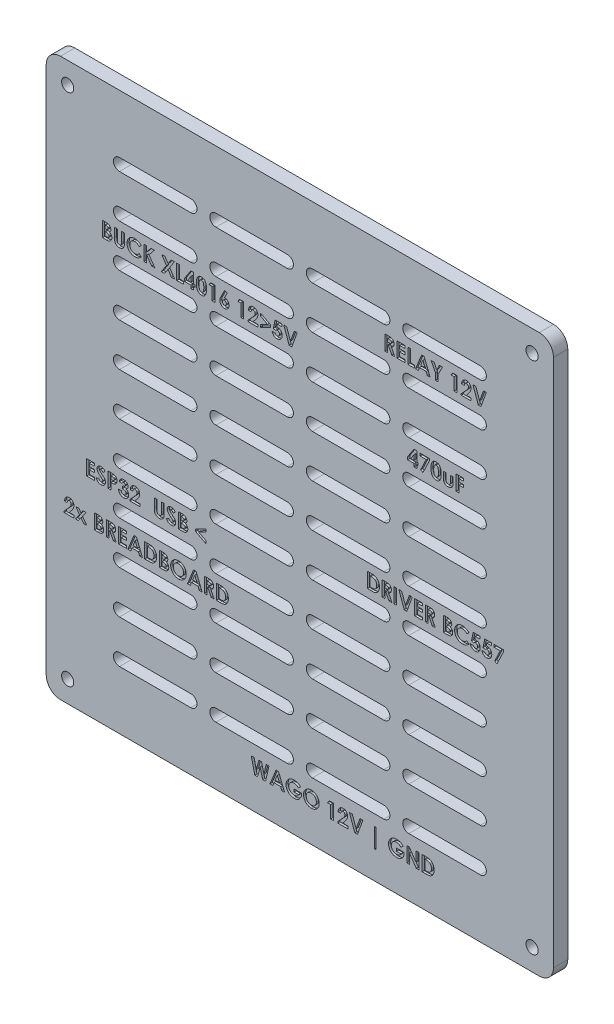
SolidWorks part; units mm, degrees
ref_plane "Front Plane" through (0, 0, 0) normal (0, 0, 1) x (1, 0, 0)
ref_plane "Top Plane" through (0, 0, 0) normal (0, 1, 0) x (1, 0, 0)
ref_plane "Right Plane" through (0, 0, 0) normal (1, 0, 0) x (0, 0, -1)
sketch "Sketch1" plane through (0, 0, 0) normal (0, 0, 1) x (1, 0, 0)
  line L0 (-67, 40) -> (67, 40)
  line L1 (71, 44) -> (71, 192)
  line L2 (67, 196) -> (-67, 196)
  line L3 (-71, 192) -> (-71, 44)
  arc A0 (-71, 44) -> (-67, 40) centre (-67, 44) ccw
  arc A1 (67, 40) -> (71, 44) centre (67, 44) ccw
  arc A2 (71, 192) -> (67, 196) centre (67, 192) ccw
  arc A3 (-67, 196) -> (-71, 192) centre (-67, 192) ccw
extrude "Plate" add sketch "Sketch1" along normal blind 4
sketch "Sketch2" plane through (0, 0, 0) normal (0, 0, 1) x (1, 0, 0)
  line L0 (-50.5, 58) -> (-30.5, 58) construction
  line L1 (-50.5, 59.7) -> (-30.5, 59.7)
  line L2 (-50.5, 56.3) -> (-30.5, 56.3)
  line L3 (-23.5, 58) -> (-3.5, 58) construction
  line L4 (-23.5, 59.7) -> (-3.5, 59.7)
  line L5 (-23.5, 56.3) -> (-3.5, 56.3)
  line L6 (3.5, 58) -> (23.5, 58) construction
  line L7 (3.5, 59.7) -> (23.5, 59.7)
  line L8 (3.5, 56.3) -> (23.5, 56.3)
  line L9 (30.5, 58) -> (50.5, 58) construction
  line L10 (30.5, 59.7) -> (50.5, 59.7)
  line L11 (30.5, 56.3) -> (50.5, 56.3)
  line L12 (-50.5, 70) -> (-30.5, 70) construction
  line L13 (-50.5, 71.7) -> (-30.5, 71.7)
  line L14 (-50.5, 68.3) -> (-30.5, 68.3)
  line L15 (-23.5, 70) -> (-3.5, 70) construction
  line L16 (-23.5, 71.7) -> (-3.5, 71.7)
  line L17 (-23.5, 68.3) -> (-3.5, 68.3)
  line L18 (3.5, 70) -> (23.5, 70) construction
  line L19 (3.5, 71.7) -> (23.5, 71.7)
  line L20 (3.5, 68.3) -> (23.5, 68.3)
  line L21 (30.5, 70) -> (50.5, 70) construction
  line L22 (30.5, 71.7) -> (50.5, 71.7)
  line L23 (30.5, 68.3) -> (50.5, 68.3)
  line L24 (-50.5, 82) -> (-30.5, 82) construction
  line L25 (-50.5, 83.7) -> (-30.5, 83.7)
  line L26 (-50.5, 80.3) -> (-30.5, 80.3)
  line L27 (-23.5, 82) -> (-3.5, 82) construction
  line L28 (-23.5, 83.7) -> (-3.5, 83.7)
  line L29 (-23.5, 80.3) -> (-3.5, 80.3)
  line L30 (3.5, 82) -> (23.5, 82) construction
  line L31 (3.5, 83.7) -> (23.5, 83.7)
  line L32 (3.5, 80.3) -> (23.5, 80.3)
  line L33 (30.5, 82) -> (50.5, 82) construction
  line L34 (30.5, 83.7) -> (50.5, 83.7)
  line L35 (30.5, 80.3) -> (50.5, 80.3)
  line L36 (-50.5, 94) -> (-30.5, 94) construction
  line L37 (-50.5, 95.7) -> (-30.5, 95.7)
  line L38 (-50.5, 92.3) -> (-30.5, 92.3)
  line L39 (-23.5, 94) -> (-3.5, 94) construction
  line L40 (-23.5, 95.7) -> (-3.5, 95.7)
  line L41 (-23.5, 92.3) -> (-3.5, 92.3)
  line L42 (3.5, 94) -> (23.5, 94) construction
  line L43 (3.5, 95.7) -> (23.5, 95.7)
  line L44 (3.5, 92.3) -> (23.5, 92.3)
  line L45 (30.5, 94) -> (50.5, 94) construction
  line L46 (30.5, 95.7) -> (50.5, 95.7)
  line L47 (30.5, 92.3) -> (50.5, 92.3)
  line L48 (-50.5, 106) -> (-30.5, 106) construction
  line L49 (-50.5, 107.7) -> (-30.5, 107.7)
  line L50 (-50.5, 104.3) -> (-30.5, 104.3)
  line L51 (-23.5, 106) -> (-3.5, 106) construction
  line L52 (-23.5, 107.7) -> (-3.5, 107.7)
  line L53 (-23.5, 104.3) -> (-3.5, 104.3)
  line L54 (3.5, 106) -> (23.5, 106) construction
  line L55 (3.5, 107.7) -> (23.5, 107.7)
  line L56 (3.5, 104.3) -> (23.5, 104.3)
  line L57 (30.5, 106) -> (50.5, 106) construction
  line L58 (30.5, 107.7) -> (50.5, 107.7)
  line L59 (30.5, 104.3) -> (50.5, 104.3)
  line L60 (-50.5, 118) -> (-30.5, 118) construction
  line L61 (-50.5, 119.7) -> (-30.5, 119.7)
  line L62 (-50.5, 116.3) -> (-30.5, 116.3)
  line L63 (-23.5, 118) -> (-3.5, 118) construction
  line L64 (-23.5, 119.7) -> (-3.5, 119.7)
  line L65 (-23.5, 116.3) -> (-3.5, 116.3)
  line L66 (3.5, 118) -> (23.5, 118) construction
  line L67 (3.5, 119.7) -> (23.5, 119.7)
  line L68 (3.5, 116.3) -> (23.5, 116.3)
  line L69 (30.5, 118) -> (50.5, 118) construction
  line L70 (30.5, 119.7) -> (50.5, 119.7)
  line L71 (30.5, 116.3) -> (50.5, 116.3)
  line L72 (-50.5, 130) -> (-30.5, 130) construction
  line L73 (-50.5, 131.7) -> (-30.5, 131.7)
  line L74 (-50.5, 128.3) -> (-30.5, 128.3)
  line L75 (-23.5, 130) -> (-3.5, 130) construction
  line L76 (-23.5, 131.7) -> (-3.5, 131.7)
  line L77 (-23.5, 128.3) -> (-3.5, 128.3)
  line L78 (3.5, 130) -> (23.5, 130) construction
  line L79 (3.5, 131.7) -> (23.5, 131.7)
  line L80 (3.5, 128.3) -> (23.5, 128.3)
  line L81 (30.5, 130) -> (50.5, 130) construction
  line L82 (30.5, 131.7) -> (50.5, 131.7)
  line L83 (30.5, 128.3) -> (50.5, 128.3)
  line L84 (-50.5, 142) -> (-30.5, 142) construction
  line L85 (-50.5, 143.7) -> (-30.5, 143.7)
  line L86 (-50.5, 140.3) -> (-30.5, 140.3)
  line L87 (-23.5, 142) -> (-3.5, 142) construction
  line L88 (-23.5, 143.7) -> (-3.5, 143.7)
  line L89 (-23.5, 140.3) -> (-3.5, 140.3)
  line L90 (3.5, 142) -> (23.5, 142) construction
  line L91 (3.5, 143.7) -> (23.5, 143.7)
  line L92 (3.5, 140.3) -> (23.5, 140.3)
  line L93 (30.5, 142) -> (50.5, 142) construction
  line L94 (30.5, 143.7) -> (50.5, 143.7)
  line L95 (30.5, 140.3) -> (50.5, 140.3)
  line L96 (-50.5, 154) -> (-30.5, 154) construction
  line L97 (-50.5, 155.7) -> (-30.5, 155.7)
  line L98 (-50.5, 152.3) -> (-30.5, 152.3)
  line L99 (-23.5, 154) -> (-3.5, 154) construction
  line L100 (-23.5, 155.7) -> (-3.5, 155.7)
  line L101 (-23.5, 152.3) -> (-3.5, 152.3)
  line L102 (3.5, 154) -> (23.5, 154) construction
  line L103 (3.5, 155.7) -> (23.5, 155.7)
  line L104 (3.5, 152.3) -> (23.5, 152.3)
  line L105 (30.5, 154) -> (50.5, 154) construction
  line L106 (30.5, 155.7) -> (50.5, 155.7)
  line L107 (30.5, 152.3) -> (50.5, 152.3)
  line L108 (-50.5, 166) -> (-30.5, 166) construction
  line L109 (-50.5, 167.7) -> (-30.5, 167.7)
  line L110 (-50.5, 164.3) -> (-30.5, 164.3)
  line L111 (-23.5, 166) -> (-3.5, 166) construction
  line L112 (-23.5, 167.7) -> (-3.5, 167.7)
  line L113 (-23.5, 164.3) -> (-3.5, 164.3)
  line L114 (3.5, 166) -> (23.5, 166) construction
  line L115 (3.5, 167.7) -> (23.5, 167.7)
  line L116 (3.5, 164.3) -> (23.5, 164.3)
  line L117 (30.5, 166) -> (50.5, 166) construction
  line L118 (30.5, 167.7) -> (50.5, 167.7)
  line L119 (30.5, 164.3) -> (50.5, 164.3)
  line L120 (-50.5, 178) -> (-30.5, 178) construction
  line L121 (-50.5, 179.7) -> (-30.5, 179.7)
  line L122 (-50.5, 176.3) -> (-30.5, 176.3)
  line L123 (-23.5, 178) -> (-3.5, 178) construction
  line L124 (-23.5, 179.7) -> (-3.5, 179.7)
  line L125 (-23.5, 176.3) -> (-3.5, 176.3)
  line L126 (3.5, 178) -> (23.5, 178) construction
  line L127 (3.5, 179.7) -> (23.5, 179.7)
  line L128 (3.5, 176.3) -> (23.5, 176.3)
  line L129 (30.5, 178) -> (50.5, 178) construction
  line L130 (30.5, 179.7) -> (50.5, 179.7)
  line L131 (30.5, 176.3) -> (50.5, 176.3)
  circle A0 centre (-65, 46) radius 1.7
  circle A1 centre (65, 46) radius 1.7
  circle A2 centre (-65, 190) radius 1.7
  circle A3 centre (65, 190) radius 1.7
  arc A4 (-50.5, 59.7) -> (-50.5, 56.3) centre (-50.5, 58) ccw
  arc A5 (-30.5, 56.3) -> (-30.5, 59.7) centre (-30.5, 58) ccw
  arc A6 (-23.5, 59.7) -> (-23.5, 56.3) centre (-23.5, 58) ccw
  arc A7 (-3.5, 56.3) -> (-3.5, 59.7) centre (-3.5, 58) ccw
  arc A8 (3.5, 59.7) -> (3.5, 56.3) centre (3.5, 58) ccw
  arc A9 (23.5, 56.3) -> (23.5, 59.7) centre (23.5, 58) ccw
  arc A10 (30.5, 59.7) -> (30.5, 56.3) centre (30.5, 58) ccw
  arc A11 (50.5, 56.3) -> (50.5, 59.7) centre (50.5, 58) ccw
  arc A12 (-50.5, 71.7) -> (-50.5, 68.3) centre (-50.5, 70) ccw
  arc A13 (-30.5, 68.3) -> (-30.5, 71.7) centre (-30.5, 70) ccw
  arc A14 (-23.5, 71.7) -> (-23.5, 68.3) centre (-23.5, 70) ccw
  arc A15 (-3.5, 68.3) -> (-3.5, 71.7) centre (-3.5, 70) ccw
  arc A16 (3.5, 71.7) -> (3.5, 68.3) centre (3.5, 70) ccw
  arc A17 (23.5, 68.3) -> (23.5, 71.7) centre (23.5, 70) ccw
  arc A18 (30.5, 71.7) -> (30.5, 68.3) centre (30.5, 70) ccw
  arc A19 (50.5, 68.3) -> (50.5, 71.7) centre (50.5, 70) ccw
  arc A20 (-50.5, 83.7) -> (-50.5, 80.3) centre (-50.5, 82) ccw
  arc A21 (-30.5, 80.3) -> (-30.5, 83.7) centre (-30.5, 82) ccw
  arc A22 (-23.5, 83.7) -> (-23.5, 80.3) centre (-23.5, 82) ccw
  arc A23 (-3.5, 80.3) -> (-3.5, 83.7) centre (-3.5, 82) ccw
  arc A24 (3.5, 83.7) -> (3.5, 80.3) centre (3.5, 82) ccw
  arc A25 (23.5, 80.3) -> (23.5, 83.7) centre (23.5, 82) ccw
  arc A26 (30.5, 83.7) -> (30.5, 80.3) centre (30.5, 82) ccw
  arc A27 (50.5, 80.3) -> (50.5, 83.7) centre (50.5, 82) ccw
  arc A28 (-50.5, 95.7) -> (-50.5, 92.3) centre (-50.5, 94) ccw
  arc A29 (-30.5, 92.3) -> (-30.5, 95.7) centre (-30.5, 94) ccw
  arc A30 (-23.5, 95.7) -> (-23.5, 92.3) centre (-23.5, 94) ccw
  arc A31 (-3.5, 92.3) -> (-3.5, 95.7) centre (-3.5, 94) ccw
  arc A32 (3.5, 95.7) -> (3.5, 92.3) centre (3.5, 94) ccw
  arc A33 (23.5, 92.3) -> (23.5, 95.7) centre (23.5, 94) ccw
  arc A34 (30.5, 95.7) -> (30.5, 92.3) centre (30.5, 94) ccw
  arc A35 (50.5, 92.3) -> (50.5, 95.7) centre (50.5, 94) ccw
  arc A36 (-50.5, 107.7) -> (-50.5, 104.3) centre (-50.5, 106) ccw
  arc A37 (-30.5, 104.3) -> (-30.5, 107.7) centre (-30.5, 106) ccw
  arc A38 (-23.5, 107.7) -> (-23.5, 104.3) centre (-23.5, 106) ccw
  arc A39 (-3.5, 104.3) -> (-3.5, 107.7) centre (-3.5, 106) ccw
  arc A40 (3.5, 107.7) -> (3.5, 104.3) centre (3.5, 106) ccw
  arc A41 (23.5, 104.3) -> (23.5, 107.7) centre (23.5, 106) ccw
  arc A42 (30.5, 107.7) -> (30.5, 104.3) centre (30.5, 106) ccw
  arc A43 (50.5, 104.3) -> (50.5, 107.7) centre (50.5, 106) ccw
  arc A44 (-50.5, 119.7) -> (-50.5, 116.3) centre (-50.5, 118) ccw
  arc A45 (-30.5, 116.3) -> (-30.5, 119.7) centre (-30.5, 118) ccw
  arc A46 (-23.5, 119.7) -> (-23.5, 116.3) centre (-23.5, 118) ccw
  arc A47 (-3.5, 116.3) -> (-3.5, 119.7) centre (-3.5, 118) ccw
  arc A48 (3.5, 119.7) -> (3.5, 116.3) centre (3.5, 118) ccw
  arc A49 (23.5, 116.3) -> (23.5, 119.7) centre (23.5, 118) ccw
  arc A50 (30.5, 119.7) -> (30.5, 116.3) centre (30.5, 118) ccw
  arc A51 (50.5, 116.3) -> (50.5, 119.7) centre (50.5, 118) ccw
  arc A52 (-50.5, 131.7) -> (-50.5, 128.3) centre (-50.5, 130) ccw
  arc A53 (-30.5, 128.3) -> (-30.5, 131.7) centre (-30.5, 130) ccw
  arc A54 (-23.5, 131.7) -> (-23.5, 128.3) centre (-23.5, 130) ccw
  arc A55 (-3.5, 128.3) -> (-3.5, 131.7) centre (-3.5, 130) ccw
  arc A56 (3.5, 131.7) -> (3.5, 128.3) centre (3.5, 130) ccw
  arc A57 (23.5, 128.3) -> (23.5, 131.7) centre (23.5, 130) ccw
  arc A58 (30.5, 131.7) -> (30.5, 128.3) centre (30.5, 130) ccw
  arc A59 (50.5, 128.3) -> (50.5, 131.7) centre (50.5, 130) ccw
  arc A60 (-50.5, 143.7) -> (-50.5, 140.3) centre (-50.5, 142) ccw
  arc A61 (-30.5, 140.3) -> (-30.5, 143.7) centre (-30.5, 142) ccw
  arc A62 (-23.5, 143.7) -> (-23.5, 140.3) centre (-23.5, 142) ccw
  arc A63 (-3.5, 140.3) -> (-3.5, 143.7) centre (-3.5, 142) ccw
  arc A64 (3.5, 143.7) -> (3.5, 140.3) centre (3.5, 142) ccw
  arc A65 (23.5, 140.3) -> (23.5, 143.7) centre (23.5, 142) ccw
  arc A66 (30.5, 143.7) -> (30.5, 140.3) centre (30.5, 142) ccw
  arc A67 (50.5, 140.3) -> (50.5, 143.7) centre (50.5, 142) ccw
  arc A68 (-50.5, 155.7) -> (-50.5, 152.3) centre (-50.5, 154) ccw
  arc A69 (-30.5, 152.3) -> (-30.5, 155.7) centre (-30.5, 154) ccw
  arc A70 (-23.5, 155.7) -> (-23.5, 152.3) centre (-23.5, 154) ccw
  arc A71 (-3.5, 152.3) -> (-3.5, 155.7) centre (-3.5, 154) ccw
  arc A72 (3.5, 155.7) -> (3.5, 152.3) centre (3.5, 154) ccw
  arc A73 (23.5, 152.3) -> (23.5, 155.7) centre (23.5, 154) ccw
  arc A74 (30.5, 155.7) -> (30.5, 152.3) centre (30.5, 154) ccw
  arc A75 (50.5, 152.3) -> (50.5, 155.7) centre (50.5, 154) ccw
  arc A76 (-50.5, 167.7) -> (-50.5, 164.3) centre (-50.5, 166) ccw
  arc A77 (-30.5, 164.3) -> (-30.5, 167.7) centre (-30.5, 166) ccw
  arc A78 (-23.5, 167.7) -> (-23.5, 164.3) centre (-23.5, 166) ccw
  arc A79 (-3.5, 164.3) -> (-3.5, 167.7) centre (-3.5, 166) ccw
  arc A80 (3.5, 167.7) -> (3.5, 164.3) centre (3.5, 166) ccw
  arc A81 (23.5, 164.3) -> (23.5, 167.7) centre (23.5, 166) ccw
  arc A82 (30.5, 167.7) -> (30.5, 164.3) centre (30.5, 166) ccw
  arc A83 (50.5, 164.3) -> (50.5, 167.7) centre (50.5, 166) ccw
  arc A84 (-50.5, 179.7) -> (-50.5, 176.3) centre (-50.5, 178) ccw
  arc A85 (-30.5, 176.3) -> (-30.5, 179.7) centre (-30.5, 178) ccw
  arc A86 (-23.5, 179.7) -> (-23.5, 176.3) centre (-23.5, 178) ccw
  arc A87 (-3.5, 176.3) -> (-3.5, 179.7) centre (-3.5, 178) ccw
  arc A88 (3.5, 179.7) -> (3.5, 176.3) centre (3.5, 178) ccw
  arc A89 (23.5, 176.3) -> (23.5, 179.7) centre (23.5, 178) ccw
  arc A90 (30.5, 179.7) -> (30.5, 176.3) centre (30.5, 178) ccw
  arc A91 (50.5, 176.3) -> (50.5, 179.7) centre (50.5, 178) ccw
  point P10 (-40.5, 58)
  point P15 (-13.5, 58)
  point P22 (13.5, 58)
  point P29 (40.5, 58)
  point P36 (-40.5, 70)
  point P43 (-13.5, 70)
  point P50 (13.5, 70)
  point P57 (40.5, 70)
  point P64 (-40.5, 82)
  point P71 (-13.5, 82)
  point P78 (13.5, 82)
  point P85 (40.5, 82)
  point P92 (-40.5, 94)
  point P99 (-13.5, 94)
  point P106 (13.5, 94)
  point P113 (40.5, 94)
  point P120 (-40.5, 106)
  point P127 (-13.5, 106)
  point P134 (13.5, 106)
  point P141 (40.5, 106)
  point P148 (-40.5, 118)
  point P155 (-13.5, 118)
  point P162 (13.5, 118)
  point P169 (40.5, 118)
  point P176 (-40.5, 130)
  point P183 (-13.5, 130)
  point P190 (13.5, 130)
  point P197 (40.5, 130)
  point P204 (-40.5, 142)
  point P211 (-13.5, 142)
  point P218 (13.5, 142)
  point P225 (40.5, 142)
  point P232 (-40.5, 154)
  point P239 (-13.5, 154)
  point P246 (13.5, 154)
  point P253 (40.5, 154)
  point P260 (-40.5, 166)
  point P267 (-13.5, 166)
  point P274 (13.5, 166)
  point P281 (40.5, 166)
  point P288 (-40.5, 178)
  point P295 (-13.5, 178)
  point P302 (13.5, 178)
  point P309 (40.5, 178)
extrude "Mounting slots" cut sketch "Sketch2" along normal through all
ref_plane "P1_Front_4" through (0, 0, 4) normal (0, 0, 1) x (1, 0, 0)
sketch "Sketch3" plane through (0, 0, 4) normal (0, 0, 1) x (1, 0, 0)
  text T0 "BUCK XL4016 12>5V" font "Century Gothic" height 4.2
  text T1 "RELAY 12V" font "Century Gothic" height 4.2
  text T2 "470uF" font "Century Gothic" height 4.2
  text T3 "ESP32  USB <" font "Century Gothic" height 4.2
  text T4 "2x BREADBOARD" font "Century Gothic" height 4.2
  text T5 "DRIVER BC557" font "Century Gothic" height 4.2
  text T6 "WAGO 12V | GND" font "Century Gothic" height 4.2
extrude "Zone labels" cut sketch "Sketch3" against normal blind 0.6
